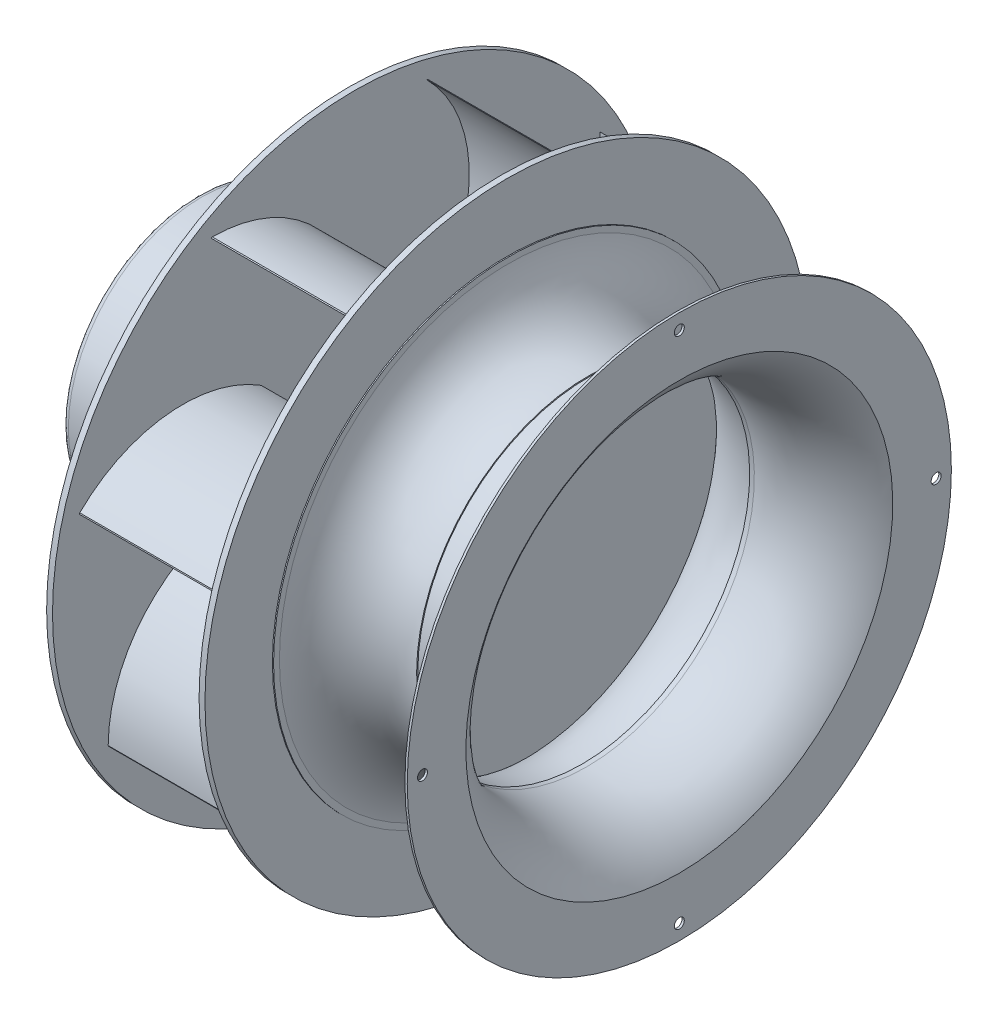
SolidWorks part; units mm, degrees
ref_plane "Front Plane" through (0, 0, 0) normal (0, 0, 1) x (1, 0, 0)
ref_plane "Top Plane" through (0, 0, 0) normal (0, 1, 0) x (1, 0, 0)
ref_plane "Right Plane" through (0, 0, 0) normal (1, 0, 0) x (0, 0, -1)
sketch "Sketch1" plane through (0, 0, 0) normal (0, 0, 1) x (1, 0, 0)
  line L0 (0, 0) -> (831.9083, 0) construction
  line L1 (0, 0) -> (0, 109)
  line L2 (5, 114) -> (70, 114)
  line L3 (70, 114) -> (70, 138)
  line L4 (70, 138) -> (90, 138)
  line L5 (90, 138) -> (90, 98)
  line L6 (90, 98) -> (95, 98)
  line L7 (95, 98) -> (95, 133)
  line L8 (95, 133) -> (105, 133)
  line L9 (105, 133) -> (105, 98)
  line L10 (105, 98) -> (130, 98)
  line L11 (130, 98) -> (130, 0)
  line L12 (130, 0) -> (0, 0)
  arc A0 (5, 114) -> (0, 109) centre (5, 109) ccw
  point P16 (0, 114)
  dimension "D10" = 5
  dimension "D1" = 114
  dimension "D2" = 24
  dimension "D3" = 70
  dimension "D4" = 40
  dimension "D5" = 35
  dimension "D6" = 5
  dimension "D7" = 20
  dimension "D8" = 10
  dimension "D9" = 60
revolve "Revolve1" add sketch "Sketch1" angle 360 about L0
sketch "Sketch2" plane through (130, 0, 0) normal (1, 0, 0) x (0, 0, -1)
  circle A0 centre (0, 0) radius 257.5
  dimension "D1" = 515
extrude "Extrude1" add sketch "Sketch2" along normal blind 5
sketch "Sketch9" plane through (130, 0, 0) normal (-1, 0, 0) x (0, 0, 1)
  circle A0 centre (0, 0) radius 252.5
  circle A1 centre (0, 0) radius 100
  circle A2 centre (0, 0) radius 257.5 construction
  dimension "D1" = 5
  dimension "D2" = 200
extrude "Extrude7" cut sketch "Sketch9" against normal blind 3
ref_plane "Plane1" through (260, 0, 0) normal (1, 0, 0) x (0, 0, -1)
sketch "Sketch3" plane through (260, 0, 0) normal (1, 0, 0) x (0, 0, -1)
  circle A0 centre (0, 0) radius 257.5
  dimension "D1" = 515
extrude "Extrude2" add sketch "Sketch3" along normal blind 5 separate body
sketch "Sketch4" plane through (135, 0, 0) normal (1, 0, 0) x (0, 0, -1)
  line L0 (0, 0) -> (0, 242.5) construction
  line L1 (0, 0) -> (128.75, 223.0015) construction
  line L2 (0, 112.5) -> (0.866, 112) construction
  line L3 (121.25, 210.0112) -> (122.116, 209.5112) construction
  line L4 (-121.25, 210.0112) -> (-122.116, 209.5112)
  line L5 (0, 112.5) -> (-0.866, 112)
  circle A0 centre (0, 0) radius 242.5 construction
  circle A1 centre (0, 0) radius 257.5 construction
  circle A2 centre (0, 0) radius 112.5 construction
  arc A3 (0, 112.5) -> (121.25, 210.0112) centre (121.9404, 85.0131) cw construction
  arc A4 (0.866, 112) -> (122.116, 209.5112) centre (122.8065, 84.5131) cw construction
  arc A5 (0, 112.5) -> (-121.25, 210.0112) centre (-121.9404, 85.0131) ccw
  arc A6 (-0.866, 112) -> (-122.116, 209.5112) centre (-122.8065, 84.5131) ccw
  dimension "D1" = 15
  dimension "D2" = 225
  dimension "D6" = 125
  dimension "D7" = 125
  dimension "D3" = 30
  dimension "D4" = 60
  dimension "D5" = 1
extrude "Extrude3" add sketch "Sketch4" along normal up to surface (130 mm away) up to face at (265, 0, -257.5)
ref_axis "Axis1" through (253.5503, 0, 0) along (-1, 0, 0)
pattern_circular "CirPattern1" count 8 over 360 about axis through (253.5503, 0, 0) along (-1, 0, 0) of "Extrude3"
sketch "Sketch5" plane through (0, 0, 0) normal (0, 0, 1) x (1, 0, 0)
  line L0 (0, 0) -> (527.2916, 0) construction
  line L1 (253.5503, 0) -> (75.411, 0) construction
  line L2 (265, 200) -> (266, 200)
  line L3 (266, 200) -> (266, 195)
  line L4 (265, 200) -> (265, 195)
  line L5 (334, 146) -> (334, 145)
  line L6 (70, 138) -> (70, -138) construction
  line L7 (265, -257.5) -> (265, 257.5) construction
  arc A0 (266, 195) -> (334, 146) centre (325.1029, 205.3367) ccw
  arc A1 (265, 195) -> (334, 145) centre (324.2891, 204.2089) ccw
  dimension "D7" = 60
  dimension "D8" = 60
  dimension "D1" = 145
  dimension "D2" = 1
  dimension "D3" = 1
  dimension "D4" = 5
  dimension "D5" = 200
  dimension "D6" = 264
revolve "Revolve2" add sketch "Sketch5" angle 360 about L0
ref_plane "Plane3" through (412, 0, 0) normal (1, 0, 0) x (0, 0, -1)
sketch "Sketch6" plane through (0, 0, 0) normal (0, 0, 1) x (1, 0, 0)
  line L0 (412, 232) -> (410, 232)
  line L1 (412, -251.35) -> (412, 251.35) construction
  line L2 (410, 232) -> (410, 182)
  line L3 (0, 0) -> (615.1417, 0) construction
  line L4 (0, 114) -> (0, -114) construction
  line L5 (253.5503, 0) -> (75.411, 0) construction
  line L6 (412, 232) -> (412, 182)
  line L7 (329, 145) -> (333, 145)
  line L8 (329, 145) -> (329, 143)
  line L9 (329, 143) -> (333, 143)
  arc A0 (333, 145) -> (410, 182) centre (342.2033, 224.4689) ccw
  arc A1 (333, 143) -> (412, 182) centre (342.9389, 222.3802) ccw
  dimension "D7" = 80
  dimension "D8" = 80
  dimension "D1" = 232
  dimension "D2" = 2
  dimension "D3" = 182
  dimension "D4" = 83
  dimension "D5" = 145
  dimension "D6" = 4
revolve "Revolve3" add sketch "Sketch6" angle 360 about L3
sketch "Sketch7" plane through (412, 0, 0) normal (1, 0, 0) x (0, 0, -1)
  line L0 (0, 0) -> (0, 219) construction
  circle A0 centre (0, 0) radius 219 construction
  circle A1 centre (0, 219) radius 4.25
  dimension "D1" = 438
  dimension "D2" = 8.5
extrude "Extrude5" cut sketch "Sketch7" against normal blind 5
pattern_circular "CirPattern2" count 4 over 360 about axis through (253.5503, 0, 0) along (-1, 0, 0) of "Extrude5"
sketch "Sketch8" plane through (0, 0, 0) normal (1, 0, 0) x (0, 0, -1)
  line L0 (0, 0) -> (0, 126) construction
  circle A0 centre (0, 0) radius 126 construction
  circle A1 centre (0, 126) radius 5
  dimension "D1" = 252
  dimension "D2" = 10
extrude "Extrude6" cut sketch "Sketch8" along normal up to surface (90 mm away) up to face at (90, 0, 138)
pattern_circular "CirPattern3" count 8 over 360 about axis through (253.5503, 0, 0) along (-1, 0, 0) of "Extrude6"
